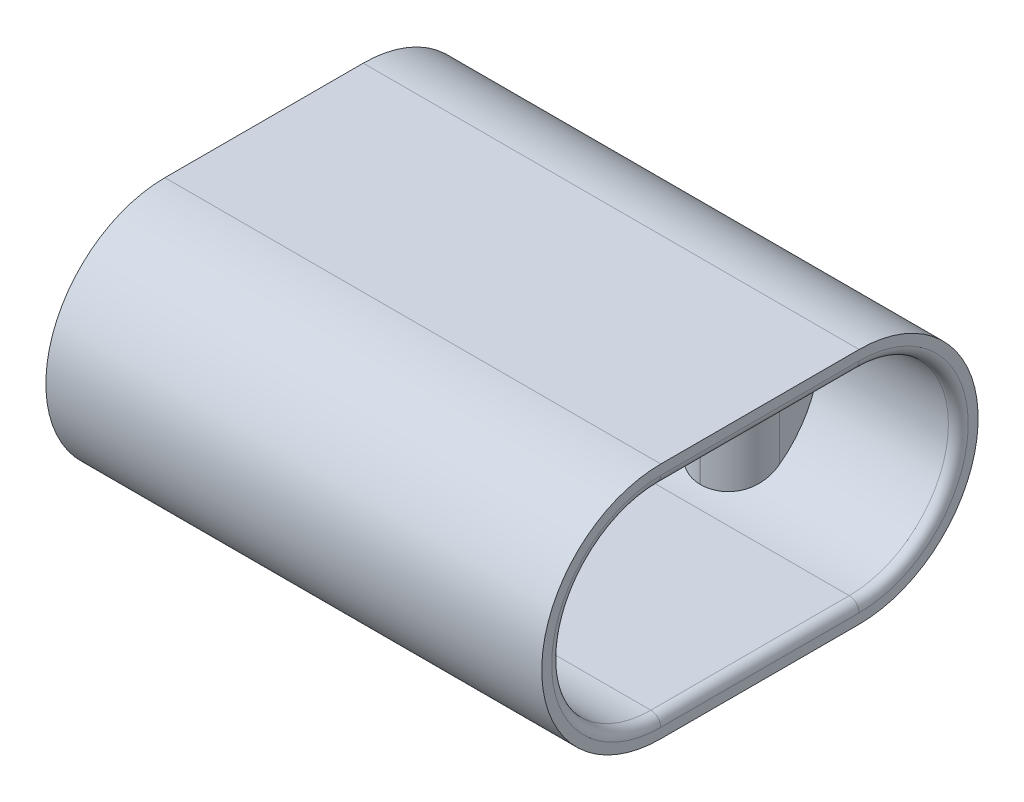
SolidWorks part; units mm, degrees
ref_plane "Front" through (0, 0, 0) normal (0, 0, 1) x (1, 0, 0)
ref_plane "Top" through (0, 0, 0) normal (0, 1, 0) x (1, 0, 0)
ref_plane "Right" through (0, 0, 0) normal (1, 0, 0) x (0, 0, -1)
sketch "Sketch2path" plane through (0, 0, 0) normal (0, 0, 1) x (1, 0, 0)
  line L1 (0, 0) -> (25, 0)
  dimension "D1" = 25
sketch "Sketch3" plane through (0, 0, 0) normal (1, 0, 0) x (0, 0, -1)
  line L6 (0, 91.8161) -> (0, -91.8161) construction
  line L7 (-5, 0) -> (5, 0) construction
  line L8 (-5, 5) -> (5, 5)
  line L9 (-5, -5) -> (5, -5)
  line L10 (-5, 6) -> (5, 6)
  line L11 (-5, -6) -> (5, -6)
  arc A6 (5, -6) -> (5, 6) centre (5, 0) ccw
  arc A7 (-5, 5) -> (-5, -5) centre (-5, 0) ccw
  arc A8 (5, -5) -> (5, 5) centre (5, 0) ccw
  arc A9 (-5, 6) -> (-5, -6) centre (-5, 0) ccw
  point P26 (0, 0)
  dimension "D1" = 6
  dimension "D2" = 5
sweep "Sweep1" add profiles "Sketch3" path "Sketch2path"
ref_point "Point1"
ref_point "Point2"
ref_axis "os podluzna" through (0, 0, 0) along (1, 0, 0)
ref_plane "Plane4 polowki" through (0, 0, 0) normal (0, 0, 1) x (1, 0, 0)
fillet "Fillet1" radius 0.5 8 edges at (25, 0, -10) (25, -5, 0) (25, 0, 10) (0, 0, 10) (0, 5, 0) (0, 0, -10) (25, 5, 0) (0, -5, 0)
sketch "Sketch13" plane through (0, 0, 0) normal (0, 1, 0) x (1, 0, 0)
  line L1 (15.99, -6) -> (16.01, -6)
  line L2 (14, -7.99) -> (14, -10)
  line L3 (14, -10) -> (18, -10)
  line L4 (18, -7.99) -> (18, -10)
  arc A0 (18, -7.99) -> (16.01, -6) centre (16.01, -7.99) ccw
  arc A1 (15.99, -6) -> (14, -7.99) centre (15.99, -7.99) ccw
  point P8 (18, -6)
  point P11 (14, -6)
  dimension "D4" = 6
  dimension "D1" = 1.99
  dimension "D2" = 14
  dimension "D3" = 18
  dimension "D5" = 10
extrude "Boss-Extrude6" add sketch "Sketch13" along normal up to next and the other way up to next
ref_plane "Plane2" through (12.5, 0, 0) normal (1, 0, 0) x (0, 0, -1)
mirror "Mirror1" about plane through (12.5, 0, 0) normal (1, 0, 0) of "Boss-Extrude6"
mirror "Mirror2" about plane through (0, 0, 0) normal (0, 0, 1) of "Mirror1"
